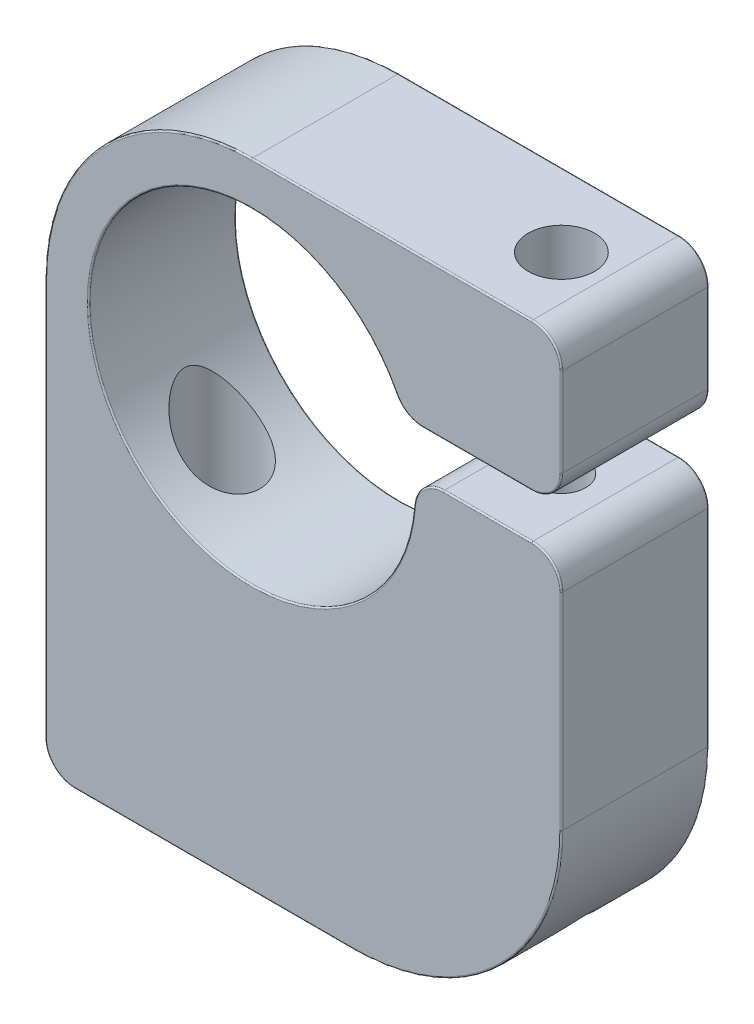
SolidWorks part; units mm, degrees
material "Сплав 2024"
ref_plane "Спереди" through (0, 0, 0) normal (0, 0, 1) x (1, 0, 0)
ref_plane "Сверху" through (0, 0, 0) normal (0, 1, 0) x (1, 0, 0)
ref_plane "Справа" through (0, 0, 0) normal (1, 0, 0) x (0, 0, -1)
sketch "Эскиз1" plane through (0, 0, 0) normal (0, 0, 1) x (1, 0, 0)
  line L0 (10.3006, 4) -> (21, 4)
  line L1 (0, 14) -> (21, 14)
  line L2 (-14, 0) -> (-14, -29)
  line L3 (-14, -29) -> (7, -29)
  line L4 (21, 14) -> (21, 4)
  line L5 (21, 1) -> (11.0047, 1)
  line L6 (21, 1) -> (21, -15)
  arc A0 (10.3006, 4) -> (11.0047, 1) centre (0, 0) ccw
  arc A1 (0, 14) -> (-14, 0) centre (0, 0) ccw
  arc A2 (7, -29) -> (21, -15) centre (7, -15) ccw
  dimension "D1" = 22.1
  dimension "D2" = 28
  dimension "D7" = 28
  dimension "D3" = 35
  dimension "D4" = 3
  dimension "D5" = 10
  dimension "D6" = 30
extrude "Бобышка-Вытянуть1" add sketch "Эскиз1" along normal blind 10
sketch "Эскиз2" plane through (0, 14, 0) normal (0, 1, 0) x (1, 0, 0)
  line L0 (21, -5) -> (1.7357, -5) construction
  line L1 (21, -10) -> (21, 0) construction
  line L2 (16, 0) -> (16, -10) construction
  line L3 (21, 0) -> (0, 0) construction
  line L4 (21, -10) -> (0, -10) construction
  dimension "D1" = 5
hole_wizard "Отверстие с зазором M41" positions "Эскиз4" profile "Эскиз3" hole size "M4" standard "Ansi Metric"
sketch "Эскиз4" plane through (0, 14, 0) normal (0, 1, 0) x (1, 0, 0)
  line L0 (16, 0) -> (16, -10) construction
  point P0 (16, -5)
sketch "Эскиз3" plane through (16, 14, 5) normal (1, 0, 0) x (0, 0, 1)
  line L0 (0, 0) -> (0, 5.3519)
  line L1 (0, 5.3519) -> (2.25, 4)
  line L2 (2.25, 4) -> (2.25, 0)
  line L5 (2.25, 0) -> (0, 0)
  line L10 (0, 5.3519) -> (-2.25, 4) construction
  line L11 (0, -6.35) -> (0, 107.95) construction
  dimension "Диаметр отверстия" = 4.5
  dimension "Глубина отверстия" = 4
  dimension "Угол заточки сверла" = 118
hole_wizard "Отверстие обработанное метчиком M4x0.71" positions "Эскиз6" profile "Эскиз5" tap size "M4x0.7" standard "Ansi Metric" end condition through all
sketch "Эскиз6" plane through (0, 1, 0) normal (0, 1, 0) x (1, 0, 0)
  line L0 (16, 0) -> (16, -10) construction
  point P0 (16, -5)
sketch "Эскиз5" plane through (16, 1, 5) normal (1, 0, 0) x (0, 0, 1)
  line L0 (0, 0) -> (0, 30)
  line L1 (0, 30) -> (1.65, 30)
  line L2 (1.65, 30) -> (1.65, 0)
  line L5 (1.65, 0) -> (0, 0)
  line L11 (0, -6.35) -> (0, 107.95) construction
  dimension "Диаметр проходного сверла" = 3.3
  dimension "Глубина проходного сверла" = 30
cosmetic thread "Отверстие резьбы1" parameters "D2"=4
sketch "Эскиз7" plane through (0, -29, 0) normal (0, -1, 0) x (1, 0, 0)
  line L0 (-14, 5) -> (0, 5) construction
  line L1 (-14, 10) -> (-14, 0) construction
  line L2 (-7, 10) -> (-7, 0) construction
  line L3 (-14, 10) -> (7, 10) construction
  line L4 (-14, 0) -> (7, 0) construction
  dimension "D1" = 7
hole_wizard "Отверстие обработанное метчиком 1/4-201" positions "Эскиз9" profile "Эскиз8" tap size "1/4-20" standard "Ansi Inch" end condition up to next
sketch "Эскиз9" plane through (0, -29, 0) normal (0, -1, 0) x (-1, 0, 0)
  line L0 (14, -5) -> (0, -5) construction
  point P0 (7, -5)
sketch "Эскиз8" plane through (-7, -29, 5) normal (1, 0, 0) x (0, 0, -1)
  line L0 (0, 0) -> (0, 20.45)
  line L1 (0, 20.45) -> (2.5527, 20.45)
  line L2 (2.5527, 20.45) -> (2.5527, 0)
  line L5 (2.5527, 0) -> (0, 0)
  line L11 (0, -6.35) -> (0, 107.95) construction
  dimension "Диаметр проходного сверла" = 5.1054
  dimension "Глубина проходного сверла" = 20.45
cosmetic thread "Отверстие резьбы2" parameters "D2"=6.35
fillet "Скругление1" radius 2 6 edges at (-14, -29, 5) (21, 14, 5) (21, 4, 5) (21, 1, 5) (11.0047, 1, 5) (10.3006, 4, 5)
fillet "Скругление2" radius 0.1 32 edges at (-9.8995, 9.8995, 10) (9.5, 14, 10) (20.4142, 13.4142, 10) (21, 9, 10) (20.4142, 4.5858, 10) (15.2944, 4, 10) (10.5494, 4.2913, 10) (-10.8286, -2.2009, 10) (11.6527, 0.4674, 10) (16.0058, 1, 10) (20.4142, 0.4142, 10) (21, -8, 10) (16.8995, -24.8995, 10) (-2.5, -29, 10) (-13.4142, -28.4142, 10) (-14, -13.5, 10) (16.8995, -24.8995, 0) (21, -8, 0) (20.4142, 0.4142, 0) (16.0058, 1, 0) (11.6527, 0.4674, 0) (-10.8286, -2.2009, 0) (10.5494, 4.2913, 0) (15.2944, 4, 0) (20.4142, 4.5858, 0) (21, 9, 0) (20.4142, 13.4142, 0) (9.5, 14, 0) (-9.8995, 9.8995, 0) (-14, -13.5, 0) (-13.4142, -28.4142, 0) (-2.5, -29, 0)
